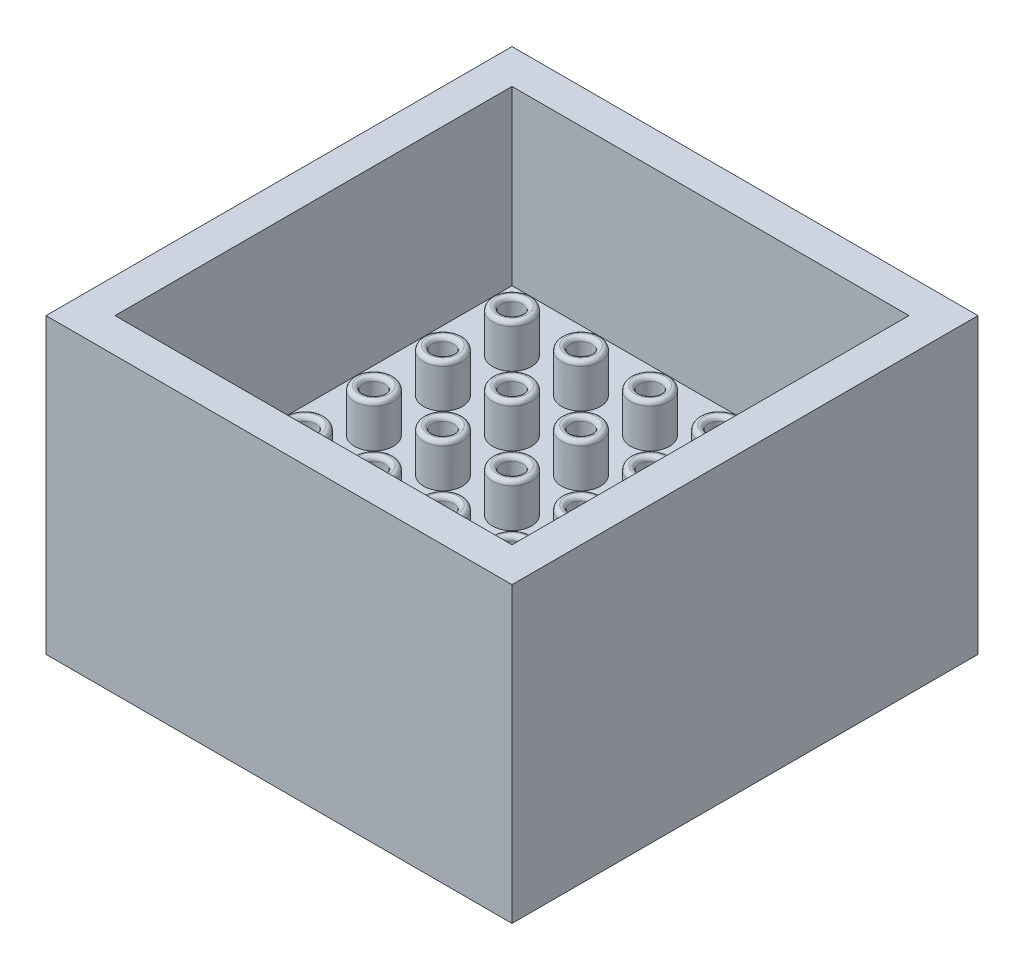
SolidWorks part; units mm, degrees
ref_plane "Front Plane" through (0, 0, 0) normal (0, 0, 1) x (1, 0, 0)
ref_plane "Top Plane" through (0, 0, 0) normal (0, 1, 0) x (1, 0, 0)
ref_plane "Right Plane" through (0, 0, 0) normal (1, 0, 0) x (0, 0, -1)
sketch "Sketch1" plane through (0, 0, 0) normal (0, 1, 0) x (1, 0, 0)
  line L0 (-13.5, 13.5) -> (13.5, 13.5)
  line L1 (-11.5, -11.5) -> (11.5, -11.5)
  line L2 (-11.5, -11.5) -> (-11.5, 11.5)
  line L3 (-11.5, 11.5) -> (11.5, 11.5)
  line L4 (11.5, -11.5) -> (11.5, 11.5)
  line L5 (-11.5, -11.5) -> (11.5, 11.5) construction
  line L6 (-11.5, 11.5) -> (11.5, -11.5) construction
  line L7 (13.5, -13.5) -> (13.5, 13.5)
  line L8 (-13.5, -13.5) -> (13.5, -13.5)
  line L9 (-13.5, -13.5) -> (-13.5, 13.5)
  point P0 (0, 0)
  dimension "D1" = 23
  dimension "D2" = 2
extrude "Boss-Extrude1" add sketch "Sketch1" along normal blind 10
sketch "Sketch2" plane through (0, 0, 0) normal (0, -1, 0) x (1, 0, 0)
  line L1 (-13.5, 13.5) -> (13.5, 13.5)
  line L2 (-13.5, 13.5) -> (-13.5, -13.5)
  line L3 (-13.5, -13.5) -> (13.5, -13.5)
  line L4 (13.5, 13.5) -> (13.5, -13.5)
  line L5 (-13.5, 13.5) -> (13.5, -13.5) construction
  line L6 (-13.5, -13.5) -> (13.5, 13.5) construction
  point P0 (0, 0)
extrude "Boss-Extrude2" add sketch "Sketch2" along normal blind 2
sketch "Sketch3" plane through (0, -2, 0) normal (0, -1, 0) x (1, 0, 0)
  line L0 (-11.5, 11.5) -> (11.5, 11.5)
  line L1 (-13.5, -13.5) -> (13.5, -13.5)
  line L2 (-13.5, -13.5) -> (-13.5, 13.5)
  line L3 (-13.5, 13.5) -> (13.5, 13.5)
  line L4 (13.5, -13.5) -> (13.5, 13.5)
  line L5 (-13.5, -13.5) -> (13.5, 13.5) construction
  line L6 (-13.5, 13.5) -> (13.5, -13.5) construction
  line L7 (11.5, -11.5) -> (11.5, 11.5)
  line L8 (-11.5, -11.5) -> (11.5, -11.5)
  line L9 (-11.5, -11.5) -> (-11.5, 11.5)
  point P0 (0, 0)
  dimension "D1" = 2
extrude "Boss-Extrude3" add sketch "Sketch3" along normal blind 5
sketch "Sketch6" plane through (0, 0, 0) normal (0, 1, 0) x (1, 0, 0)
  line L0 (11.5, -11.5) -> (11.5, 11.5) construction
  line L1 (11.5, 11.5) -> (-11.5, 11.5) construction
  circle A0 centre (8, 8) radius 1.125
  dimension "D2" = 2.25
  dimension "D1" = 3.5
  dimension "D3" = 3.5
extrude "Boss-Extrude5" add sketch "Sketch6" along normal blind 2.5
sketch "Sketch7" plane through (0, 2.5, 0) normal (0, 1, 0) x (1, 0, 0)
  circle A0 centre (8, 8) radius 0.625
  dimension "D1" = 1.25
extrude "Cut-Extrude2" cut sketch "Sketch7" against normal up to next
fillet "Fillet3" radius 0.25 2 edges at (8, 2.5, -6.875) (8, 2.5, -7.375)
pattern_linear "LPattern1" count 5 spacing 4 along (0, 0, 1) count 5 spacing 4 along (-1, 0, 0) of "Boss-Extrude5", "Cut-Extrude2", "Fillet3"
equation "\"D3@Sketch6\"=\"D1@Sketch6\""
